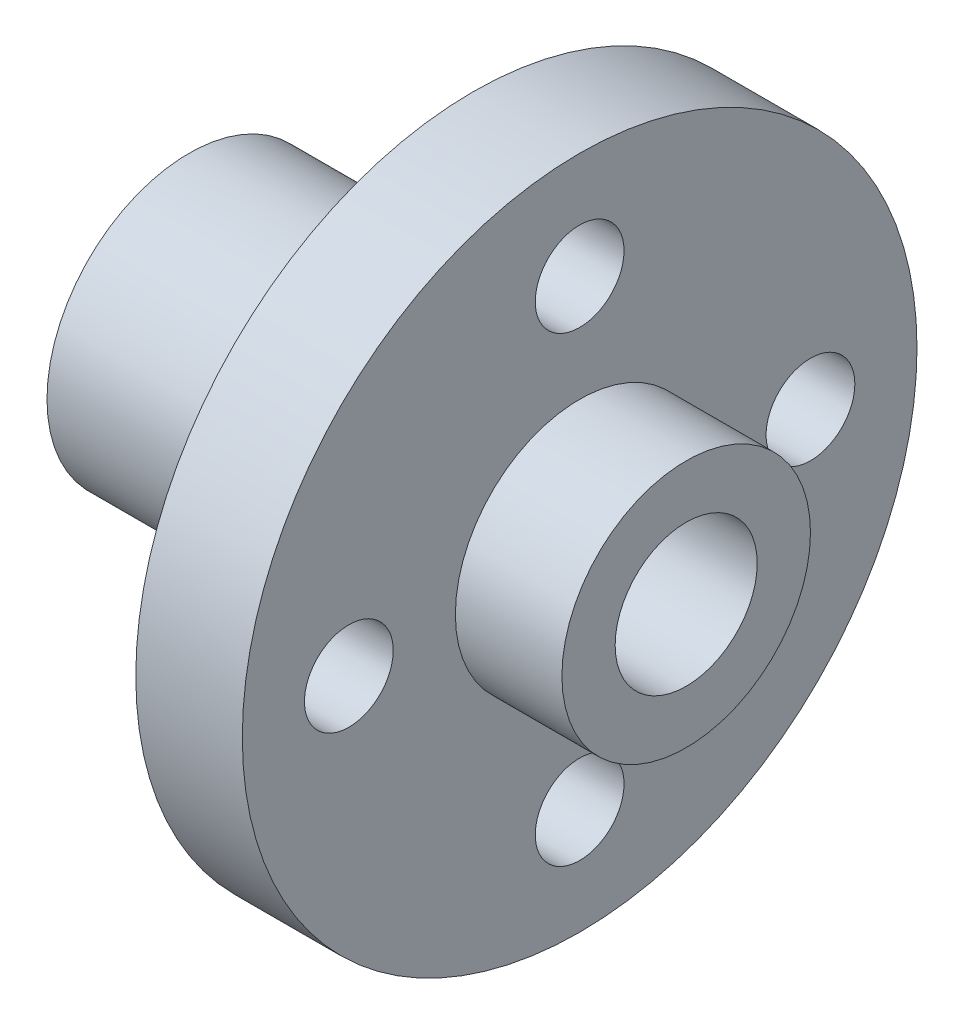
SolidWorks part; units mm, degrees
note: The reader was unsure of these and kept them because the rebuilt part matched: shared geometry of "Sketch1<3>", "Sketch1<4>".
material "Brass"
ref_plane "Front Plane" through (0, 0, 0) normal (0, 0, 1) x (1, 0, 0)
ref_plane "Top Plane" through (0, 0, 0) normal (0, 1, 0) x (1, 0, 0)
ref_plane "Right Plane" through (0, 0, 0) normal (1, 0, 0) x (0, 0, -1)
sketch "Sketch1" plane through (0, 0, 0) normal (1, 0, 0) x (0, 0, -1)
  circle A0 centre (0, 0) radius 9.5
  circle A1 centre (0, 0) radius 4
  circle A2 centre (0, 0) radius 3.5
  circle A3 centre (0, 0) radius 2
  circle A4 centre (0, 0) radius 6.5 construction
  circle A5 centre (0, 6.5) radius 1.25
  circle A6 centre (6.5, 0) radius 1.25
  circle A7 centre (0, -6.5) radius 1.25
  circle A8 centre (-6.5, 0) radius 1.25
  point P9 (-6.0627, -2.3439)
  point P10 (-6.378, -1.2533)
  point P11 (0, 0)
  point P18 (0, 0)
  dimension "D1" = 19
  dimension "D2" = 8
  dimension "D3" = 7
  dimension "D4" = 4
  dimension "D5" = 13
  dimension "D6" = 2.5
  dimension "D7" = 4
extrude "Boss-Extrude1" add sketch "Sketch1" along normal blind 3 contours A0 A8 A7 A6 A5 A1 | A1 A2
extrude "Boss-Extrude2" add sketch "Sketch1<3>" along normal blind 6 contours A2 A3
sketch "Sketch1<3>" plane through (0, 0, 0) normal (1, 0, 0) x (0, 0, -1) same geometry as "Sketch1"
extrude "Boss-Extrude3" add sketch "Sketch1<4>" against normal blind 8 contours A1 A2 | A2 A3
sketch "Sketch1<4>" plane through (0, 0, 0) normal (1, 0, 0) x (0, 0, -1) same geometry as "Sketch1"
cosmetic thread "Cosmetic Thread1" parameters "D2"=6.619
sketch "Sketch2" plane through (-8, 0, 0) normal (-1, 0, 0) x (0, 0, 1)
  circle A0 centre (0, 0) radius 3.5
  dimension "D1" = 7
extrude "Cut-Extrude1" cut sketch "Sketch2" against normal up to next (8 mm away) draft 45
